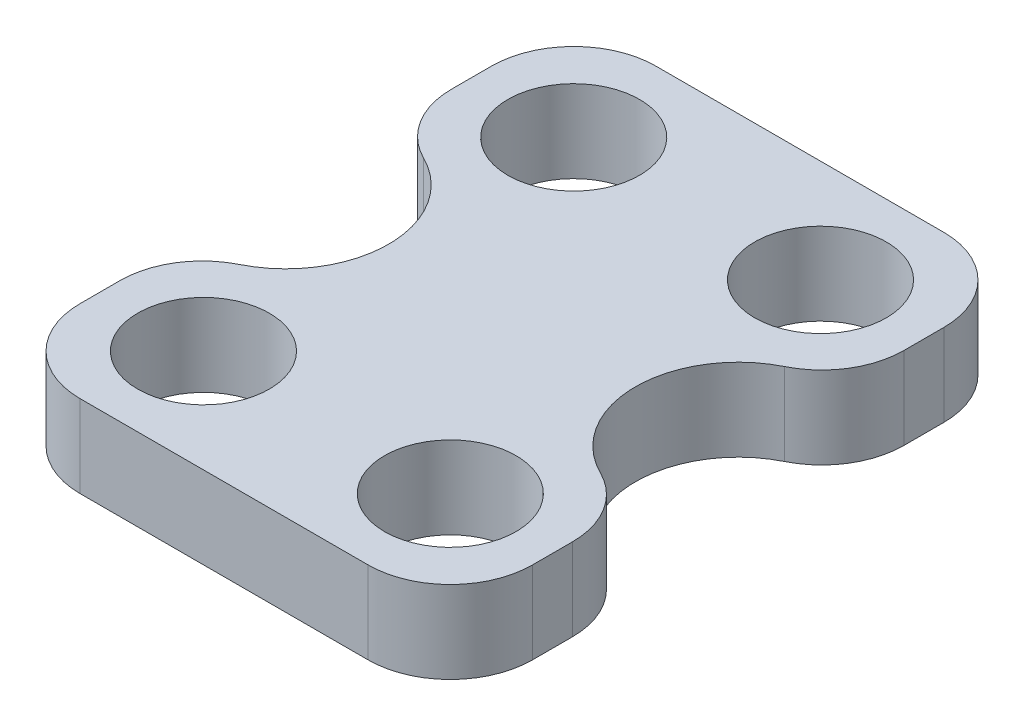
SolidWorks part; units mm, degrees
ref_plane "Front Plane" through (0, 0, 0) normal (0, 0, 1) x (1, 0, 0)
ref_plane "Top Plane" through (0, 0, 0) normal (0, 1, 0) x (1, 0, 0)
ref_plane "Right Plane" through (0, 0, 0) normal (1, 0, 0) x (0, 0, -1)
sketch "Sketch1" plane through (0, 0, 0) normal (0, 1, 0) x (1, 0, 0)
  line L1 (-2.5, 2.5) -> (8.5, 2.5)
  line L2 (-2.5, 2.5) -> (-2.5, -11.5)
  line L3 (-2.5, -11.5) -> (8.5, -11.5)
  line L4 (8.5, 2.5) -> (8.5, -11.5)
  circle A0 centre (0, 0) radius 1.6
  circle A1 centre (6, 0) radius 1.6
  circle A2 centre (0, -9) radius 1.6
  circle A3 centre (6, -9) radius 1.6
  dimension "D1" = 3.2
  dimension "D2" = 9
  dimension "D3" = 6
  dimension "D4" = 2.5
  dimension "D5" = 2.5
  dimension "D6" = 2.5
  dimension "D7" = 2.5
extrude "Boss-Extrude1" add sketch "Sketch1" along normal blind 2
fillet "Fillet1" radius 2 4 edges at (-2.5, 1, 11.5) (8.5, 1, 11.5) (8.5, 1, -2.5) (-2.5, 1, -2.5)
sketch "Sketch2" plane through (0, 2, 0) normal (0, 1, 0) x (1, 0, 0)
  line L0 (-2.5, 0.5) -> (-2.5, -9.5) construction
  line L1 (8.5, -9.5) -> (8.5, 0.5) construction
  circle A0 centre (-2.5, -4.5) radius 2.5
  circle A1 centre (8.5, -4.5) radius 2.5
  dimension "D1" = 5
extrude "Cut-Extrude1" cut sketch "Sketch2" against normal through all
fillet "Fillet2" radius 2 4 edges at (-2.5, 1, 7) (8.5, 1, 7) (8.5, 1, 2) (-2.5, 1, 2)
